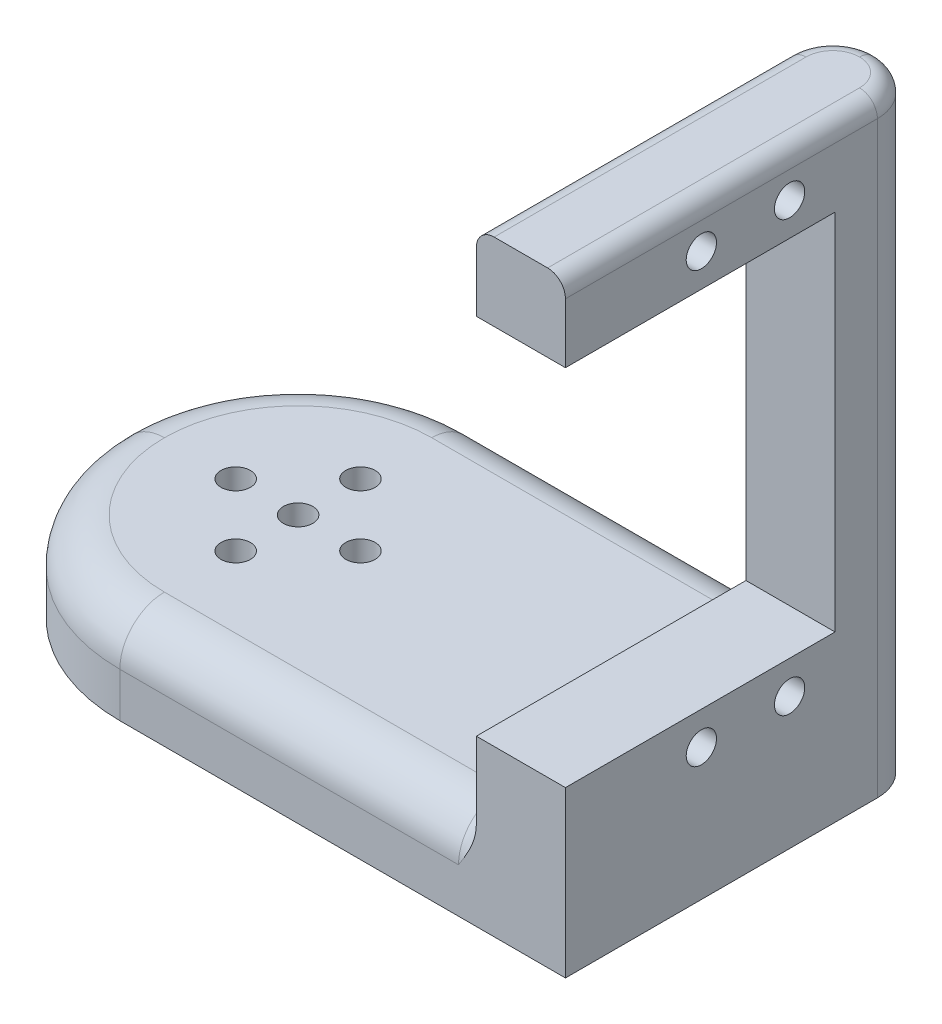
SolidWorks part; units mm, degrees
ref_plane "Front Plane" through (0, 0, 0) normal (0, 0, 1) x (1, 0, 0)
ref_plane "Top Plane" through (0, 0, 0) normal (0, 1, 0) x (1, 0, 0)
ref_plane "Right Plane" through (0, 0, 0) normal (1, 0, 0) x (0, 0, -1)
sketch "Sketch1" plane through (0, 0, 0) normal (0, 0, 1) x (1, 0, 0)
  line L0 (0, 0) -> (0, 68)
  line L1 (0, 68) -> (-10, 68)
  line L2 (-10, 68) -> (-10, 10)
  line L3 (-10, 10) -> (-70, 10)
  line L4 (-70, 10) -> (-70, 0)
  line L5 (-70, 0) -> (0, 0)
  dimension "D1" = 68
  dimension "D2" = 58
  dimension "D3" = 10
  dimension "D4" = 70
extrude "Boss-Extrude2" add sketch "Sketch1" along normal blind 40
sketch "Sketch3" plane through (0, 0, 0) normal (1, 0, 0) x (0, 0, -1)
  line L0 (-9.75, 18.5) -> (-9.75, 59.3)
  line L1 (-9.75, 59.3) -> (-40, 59.3)
  line L2 (-40, 0) -> (-40, 68) construction
  line L3 (-40, 59.3) -> (-40, 18.5)
  line L4 (-40, 18.5) -> (-9.75, 18.5)
  line L5 (-9.75, 38.9) -> (-27.1227, 38.9) construction
  circle A0 centre (-14.85, 63) radius 1.7
  circle A1 centre (-24.75, 63) radius 1.7
  circle A2 centre (-24.75, 14.8) radius 1.7
  circle A3 centre (-14.85, 14.8) radius 1.7
  dimension "D8" = 3.4
  dimension "D9" = 3.4
  dimension "D1" = 30.25
  dimension "D2" = 40.8
  dimension "D3" = 18.5
  dimension "D4" = 3.7
  dimension "D5" = 3.7
  dimension "D6" = 9.9
  dimension "D7" = 5.1
extrude "Cut-Extrude1" cut sketch "Sketch3" against normal up to next
sketch "Sketch4" plane through (0, 0, 0) normal (0, -1, 0) x (1, 0, 0)
  line L0 (0, 40) -> (0, 0) construction
  circle A0 centre (-50, 20) radius 1.65
  circle A1 centre (-50, 20) radius 7 construction
  circle A2 centre (-50, 13) radius 1.65
  circle A3 centre (-43, 20) radius 1.65
  circle A4 centre (-50, 27) radius 1.65
  circle A5 centre (-57, 20) radius 1.65
  dimension "D1" = 3.3
  dimension "D2" = 14
  dimension "D3" = 50
extrude "Cut-Extrude2" cut sketch "Sketch4" against normal up to next
fillet "Fillet1" radius 5 5 edges at (-10, 39, 0) (0, 34, 0) (-40, 10, 40) (-40, 10, 0) (-70, 10, 20)
fillet "Fillet2" radius 2 7 edges at (0, 68, 22.5) (-1.4645, 68, 1.4645) (-8.5355, 68, 1.4645) (-10, 8.5355, 38.5355) (-8.5355, 8.5355, 1.4645) (-10, 68, 22.5) (-10, 10, 20)
fillet "Fillet3" radius 20 4 edges at (-68.5355, 8.5355, 38.5355) (-68.5355, 8.5355, 1.4645) (-70, 2.5, 0) (-70, 2.5, 40)
equation "\"D1@Sketch3\"=0.975+2.05"
equation "\"D5@Sketch3\"=\"D4@Sketch3\""
equation "\"D9@Sketch3\"=\"D8@Sketch3\""
